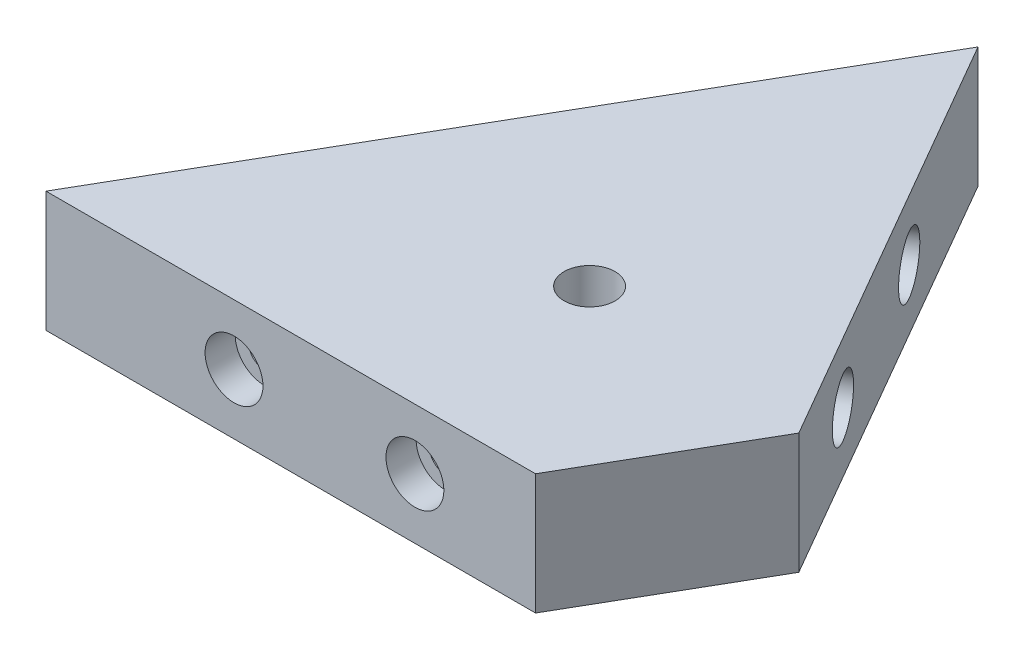
SolidWorks part; units mm, degrees
material "1023 Carbon Steel Sheet (SS)"
ref_plane "Front Plane" through (0, 0, 0) normal (0, 0, 1) x (1, 0, 0)
ref_plane "Top Plane" through (0, 0, 0) normal (0, 1, 0) x (1, 0, 0)
ref_plane "Right Plane" through (0, 0, 0) normal (1, 0, 0) x (0, 0, -1)
sketch "Sketch1" plane through (0, 0, 0) normal (0, 1, 0) x (1, 0, 0)
  line L0 (159.6594, -241.1624) -> (-297.5406, 22.8022) construction
  line L1 (-145.1406, 286.7667) -> (-449.9406, -241.1624) construction
  line L2 (-449.9406, -241.1624) -> (159.6594, -241.1624) construction
  line L3 (159.6594, -241.1624) -> (-145.1406, 286.7667) construction
  line L4 (93.6683, -241.1624) -> (93.6683, -203.0624) construction
  line L5 (119.0683, -241.1624) -> (129.2161, -223.5859)
  line L6 (55.5683, -241.1624) -> (55.5683, -181.0653) construction
  line L7 (15.9736, -241.1624) -> (51.8951, -178.9446)
  line L8 (15.9736, -241.1624) -> (119.0683, -241.1624)
  line L9 (51.8951, -178.9446) -> (129.2161, -223.5859)
  line L10 (93.6683, -203.0624) -> (55.5683, -203.0624) construction
  dimension "D1" = 609.6
  dimension "D2" = 38.1
  dimension "D3" = 25.4
  dimension "D4" = 38.1
  dimension "D6" = 40.5911
  dimension "D5" = 15.24
  dimension "D7" = 103.0947
  dimension "D8" = 60
  dimension "D9" = 120
extrude "Boss-Extrude1" add sketch "Sketch1" along normal blind 25.4
sketch "Sketch2" plane through (0, 0, 241.1624) normal (0, 0, 1) x (1, 0, 0)
  line L0 (15.9736, 0) -> (119.0683, 0) construction
  line L1 (15.9736, 0) -> (15.9736, 25.4) construction
  line L2 (119.0683, 0) -> (119.0683, 25.4) construction
  line L3 (15.9736, 25.4) -> (119.0683, 25.4) construction
  line L4 (15.9736, 0) -> (119.0683, 25.4) construction
  line L5 (119.0683, 0) -> (15.9736, 25.4) construction
  line L6 (93.6683, 25.4) -> (93.6683, 0) construction
  line L7 (55.5683, 0) -> (55.5683, 25.4) construction
  circle A0 centre (55.5683, 12.7) radius 6.096
  circle A1 centre (93.6683, 12.7) radius 6.096
  point P6 (67.521, 12.7)
  point P15 (-5.5874, 8.785)
  dimension "D4" = 12.192
  dimension "D5" = 12.192
  dimension "D1" = 25.4
  dimension "D2" = 25.4
  dimension "D3" = 38.1
extrude "Cut-Extrude1" cut sketch "Sketch2" against normal blind 6.35
sketch "Sketch3" plane through (0, 0, 234.8124) normal (0, 0, 1) x (1, 0, 0)
  circle A0 centre (55.5683, 12.7) radius 3.2639
  dimension "D1" = 6.5278
extrude "Cut-Extrude2" cut sketch "Sketch3" against normal blind 16.51
sketch "Sketch4" plane through (0, 0, 234.8124) normal (0, 0, 1) x (1, 0, 0)
  circle A0 centre (93.6683, 12.7) radius 3.2639
  dimension "D1" = 6.5278
extrude "Cut-Extrude3" cut sketch "Sketch4" against normal blind 16.51
mirror "Mirror1" about plane through (51.8951, 25.4, 178.9446) normal (-0.5, 0, 0.866) of "Boss-Extrude1", "Cut-Extrude1", "Cut-Extrude2", "Cut-Extrude3"
sketch "Sketch5" plane through (0, 25.4, 0) normal (0, 1, 0) x (1, 0, 0)
  line L0 (87.8165, -116.7268) -> (15.9736, -241.1624) construction
  line L1 (15.9736, -241.1624) -> (119.0683, -241.1624) construction
  line L2 (119.0683, -241.1624) -> (139.3639, -206.0094) construction
  line L3 (139.3639, -206.0094) -> (87.8165, -116.7268) construction
  line L4 (51.8951, -178.9446) -> (129.2161, -223.5859) construction
  circle A0 centre (90.5556, -201.2653) radius 5.3578
  dimension "D1" = 10.7156
  dimension "D2" = 44.6413
  dimension "D3" = 71.8429
extrude "Cut-Extrude4" cut sketch "Sketch5" against normal through all
ref_plane "Plane1" through (0, 0, 241.1624) normal (0, 0, 1) x (1, 0, 0)
equation "\"bplate_length\"= 24in"
equation "\"bplate_height\"= 6in"
equation "\"bplate_thickness\"= 0.5in"
equation "\"connector_plate_hole_diameter\"= 0.375in"
equation "\"connector_plate_hole_depth\"= 1in"
equation "\"connector_plate_thickness\"= 1in"
equation "\"D1@Sketch1\"=\"bplate_length\""
